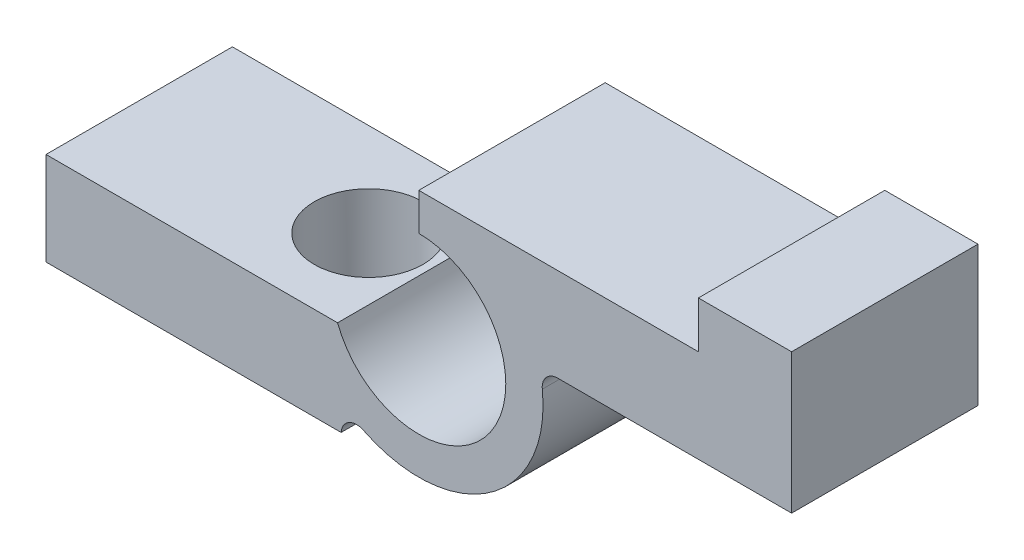
SolidWorks part; units mm, degrees
ref_plane "Front Plane" through (0, 0, 0) normal (0, 0, 1) x (1, 0, 0)
ref_plane "Top Plane" through (0, 0, 0) normal (0, 1, 0) x (1, 0, 0)
ref_plane "Right Plane" through (0, 0, 0) normal (1, 0, 0) x (0, 0, -1)
ref_plane "Plano1"
sketch "Esboço1" plane through (0, 0, 0) normal (0, 0, 1) x (1, 0, 0)
  line L0 (0, 0) -> (6.5, 0)
  line L1 (6.5, 0) -> (6.5, 3)
  line L2 (6.5, 3) -> (0, 3)
  line L3 (0, 3) -> (0, 0)
  line L4 (9, 5) -> (18, 5)
  line L5 (18, 5) -> (18, 8)
  line L6 (18, 8) -> (9, 8)
  line L7 (9, 8) -> (9, 5)
  circle A0 centre (9, 4) radius 4
  dimension "D5" = 8
  dimension "D1" = 6.5
  dimension "D2" = 3
  dimension "D3" = 9.8489
  dimension "D4" = 9.8489
  dimension "D6" = 12.0416
  dimension "D7" = 3
  dimension "D8" = 19.6977
extrude "Extrude1_Corpo" add sketch "Esboço1" along normal blind 6 contours L2 A0 L1 | L4 A0 L7 | A0 L2 L3 L0 L1 | A0 L4 L5 L6 | L7 A0 L2 L1 L4
sketch "Esboço2" plane through (0, 0, 0) normal (0, 0, -1) x (-1, 0, 0)
  circle A0 centre (-9, 4) radius 2.8
  dimension "D3" = 5.6
  dimension "D1" = 9.8489
  dimension "D2" = 9.8489
extrude "Furo_Anel" cut sketch "Esboço2" against normal through all and the other way through all
sketch "Esboço3" plane through (0, 0, 0) normal (0, 0, -1) x (-1, 0, 0)
  line L0 (-3, 3) -> (-9, 3)
  line L1 (-9, 3) -> (-9, 9)
  line L2 (-9, 9) -> (-3, 9)
  line L3 (-3, 9) -> (-3, 3)
  dimension "D1" = 9.4868
  dimension "D2" = 4.2426
  dimension "D3" = 4.2426
  dimension "D4" = 9.4868
extrude "Abertura_C" cut sketch "Esboço3" against normal through all and the other way through all
fillet "Fillet_Juncoes" radius 0.5 2 edges at (12.873, 5, 3) (6.5, 0.8775, 3)
sketch "Esboço4" plane through (0, 0, 0) normal (-1, 0, 0) x (0, 0, 1)
  line L4 (0, 3) -> (0, 0)
  line L5 (0, 0) -> (6, 0)
  line L6 (6, 0) -> (6, 3)
  line L7 (6, 3) -> (0, 3)
  line L8 (0, 3) -> (0, 0)
  line L9 (0, 0) -> (6, 0)
  line L10 (6, 0) -> (6, 3)
  line L11 (6, 3) -> (0, 3)
  dimension "D1" = 0
extrude "Ressalto-extrusão2" add sketch "Esboço4" along normal blind 3
sketch "Esboço5" plane through (18, 0, 0) normal (1, 0, 0) x (0, 0, -1)
  line L4 (0, 5) -> (0, 8)
  line L5 (0, 8) -> (-6, 8)
  line L6 (-6, 8) -> (-6, 5)
  line L7 (-6, 5) -> (0, 5)
  line L8 (0, 5) -> (0, 8)
  line L9 (0, 8) -> (-6, 8)
  line L10 (-6, 8) -> (-6, 5)
  line L11 (-6, 5) -> (0, 5)
  dimension "D1" = 0
extrude "Ressalto-extrusão3" add sketch "Esboço5" along normal blind 3 separate body
sketch "Esboço6" plane through (0, 8, 0) normal (0, 1, 0) x (1, 0, 0)
  line L4 (18, 0) -> (18, -6)
  line L5 (18, -6) -> (21, -6)
  line L6 (21, -6) -> (21, 0)
  line L7 (21, 0) -> (18, 0)
  line L8 (18, 0) -> (18, -6)
  line L9 (18, -6) -> (21, -6)
  line L10 (21, -6) -> (21, 0)
  line L11 (21, 0) -> (18, 0)
  dimension "D1" = 0
extrude "Ressalto-extrusão4" add sketch "Esboço6" along normal blind 1.5
sketch "Esboço7" plane through (0, 3, 0) normal (0, 1, 0) x (1, 0, 0)
  line L0 (6.3847, 0) -> (6.3847, -6) construction
  line L1 (4.3847, -3) -> (6.3847, -3) construction
  circle A0 centre (4.3847, -3) radius 1.75
  dimension "D2" = 3.5
  dimension "D1" = 2
extrude "Corte-extrusão3" cut sketch "Esboço7" against normal through all both and the other way through all
